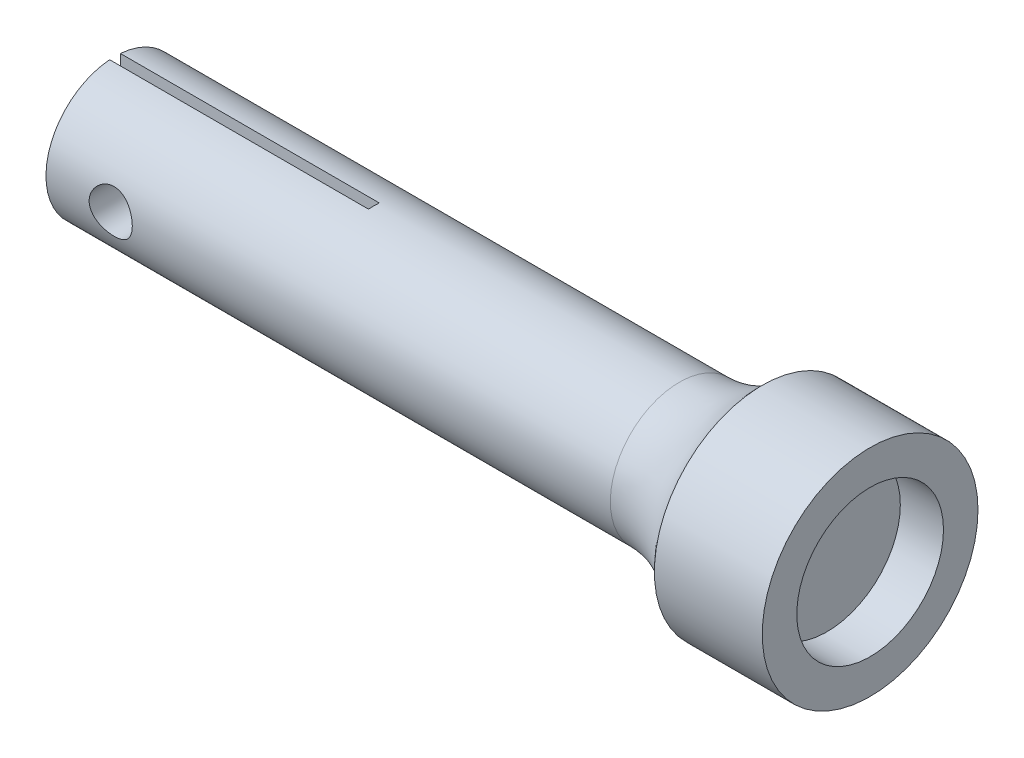
SolidWorks part; units mm, degrees
ref_plane "前视基准面" through (0, 0, 0) normal (0, 0, 1) x (1, 0, 0)
ref_plane "上视基准面" through (0, 0, 0) normal (0, 1, 0) x (1, 0, 0)
ref_plane "右视基准面" through (0, 0, 0) normal (1, 0, 0) x (0, 0, -1)
other "Configuration Table"
sketch "草图1" plane through (0, 0, 0) normal (1, 0, 0) x (0, 0, -1)
  circle A0 centre (0, 0) radius 3.2
  dimension "D1" = 6.4
extrude "凸台-拉伸1" add sketch "草图1" along normal blind 30
sketch "草图2" plane through (0, 0, 0) normal (-1, 0, 0) x (0, 0, 1)
  line L0 (0, 3.2) -> (0, -3.2) construction
  line L2 (-0.25, 3.862) -> (0.25, 3.862)
  line L3 (-0.25, 3.862) -> (-0.25, -2.5924)
  line L4 (-0.25, -2.5924) -> (0.25, -2.5924)
  line L5 (0.25, 3.862) -> (0.25, -2.5924)
  circle A0 centre (0, 0) radius 3.2 construction
  dimension "D1" = 0.5
  dimension "D2" = 0.25
extrude "切除-拉伸1" cut sketch "草图2" against normal blind 12
sketch "草图3" plane through (0, 0, 0.25) normal (0, 0, -1) x (-1, 0, 0)
  line L0 (0, -0.0049) -> (-6.0327, -0.0049) construction
  line L1 (0, -3.2) -> (0, 3.1902) construction
  circle A0 centre (-3, -0.0049) radius 1
  dimension "D1" = 2
  dimension "D2" = 3
extrude "切除-拉伸2" cut sketch "草图3" against normal blind 10 and the other way blind 10
sketch "草图6" plane through (30, 0, 0) normal (1, 0, 0) x (0, 0, -1)
  circle A0 centre (0, 0) radius 5
  dimension "D1" = 10
extrude "凸台-拉伸2" add sketch "草图6" along normal blind 5
fillet "圆角1" radius 5 1 edges at (30, 0, -3.2)
sketch "草图7" plane through (35, 0, 0) normal (1, 0, 0) x (0, 0, -1)
  circle A0 centre (0, 0) radius 3.4
  dimension "D1" = 6.8
extrude "切除-拉伸3" cut sketch "草图7" against normal blind 2
